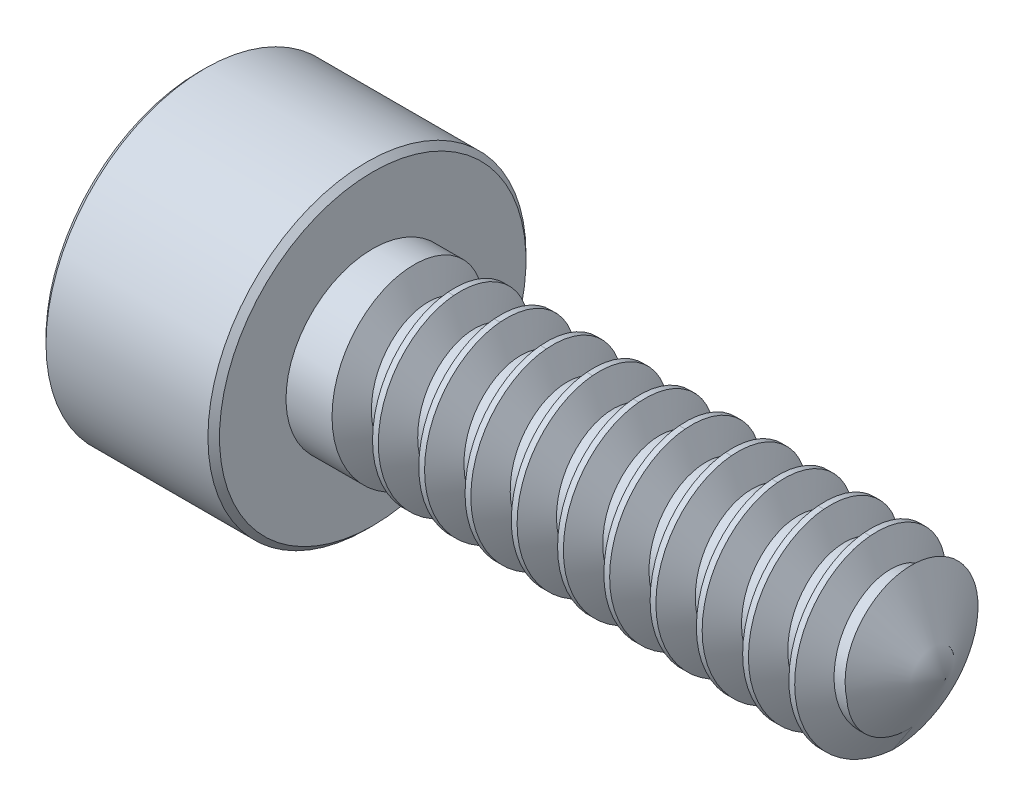
SolidWorks part; units mm, degrees
ref_plane "Front Plane" through (0, 0, 0) normal (0, 0, 1) x (1, 0, 0)
ref_plane "Top Plane" through (0, 0, 0) normal (0, 1, 0) x (1, 0, 0)
ref_plane "Right Plane" through (0, 0, 0) normal (1, 0, 0) x (0, 0, -1)
sketch "Sketch1" plane through (0, 0, 0) normal (0, 0, 1) x (1, 0, 0)
  line L0 (0, 0) -> (0, 2.75)
  line L1 (0, 2.75) -> (3, 2.75)
  line L2 (3, 2.75) -> (3, 1.5)
  line L3 (3, 1.5) -> (12, 1.5)
  line L4 (12, 1.5) -> (12.9013, 0)
  line L5 (12.9013, 0) -> (0, 0) construction
  line L6 (0, 0) -> (12.9013, 0)
  point P3 (14.8605, 0)
  point P8 (14.4199, 0)
  dimension "D1" = 5.5
  dimension "D2" = 3
  dimension "D3" = 3
  dimension "D4" = 9
  dimension "D5" = 59
revolve "Revolve1" add sketch "Sketch1" angle 360 about L5
thread "Thread1" pitch 0.8 method cut profile "Thread Profile1" start angle 0, offset 2, length 11, pitch 0.8, diameter 3
ref_plane "Plane1" through (14.9013, 0, 1.5) normal (0, -1, 0) x (0, 0, 1)
sketch "Thread Profile1" plane through (14.9013, 0, 1.5) normal (0, -1, 0) x (0, 0, 1)
  line L0 (0, 0) -> (0, 0.8) construction
  line L11 (0, 0) -> (0, 0.7)
  line L12 (0, 0.7) -> (-0.433, 0.45)
  line L13 (-0.433, 0.45) -> (-0.433, 0.25)
  line L15 (-0.433, 0.25) -> (0, 0)
  line L17 (-0.433, 0.35) -> (0, 0.35) construction
  point P2 (0, 0)
  dimension "Pitch" = 0.8
  dimension "Profile_Angle" = 60
  dimension "Profile_Land" = 0.2
  dimension "Profile_Height" = 0.433
sketch "Sketch5" plane through (0, 0, 0) normal (-1, 0, 0) x (0, 0, 1)
  line L1 (0, -1.4434) -> (1.25, -0.7217)
  line L2 (1.25, -0.7217) -> (1.25, 0.7217)
  line L3 (1.25, 0.7217) -> (0, 1.4434)
  line L4 (0, 1.4434) -> (-1.25, 0.7217)
  line L5 (-1.25, 0.7217) -> (-1.25, -0.7217)
  line L6 (-1.25, -0.7217) -> (0, -1.4434)
  circle A0 centre (0, 0) radius 1.25 construction
  circle A1 centre (0, 0) radius 2.75
  point P1 (0, -2.75)
  point P11 (0, 0)
  dimension "D1" = 2.5
extrude "Cut-Extrude1" cut sketch "Sketch5" against normal blind 1.3 contours L1 L2 L3 L4 L5 L6
chamfer "Chamfer1" distance 0.1 angle 45 8 edges at (0, 0, -1.25) (0, -1.0825, -0.625) (0, -1.0825, 0.625) (0, 0, 1.25) (0, 1.0825, 0.625) (0, 1.0825, -0.625) (3, 2.75, 0) (0, 2.75, 0)
